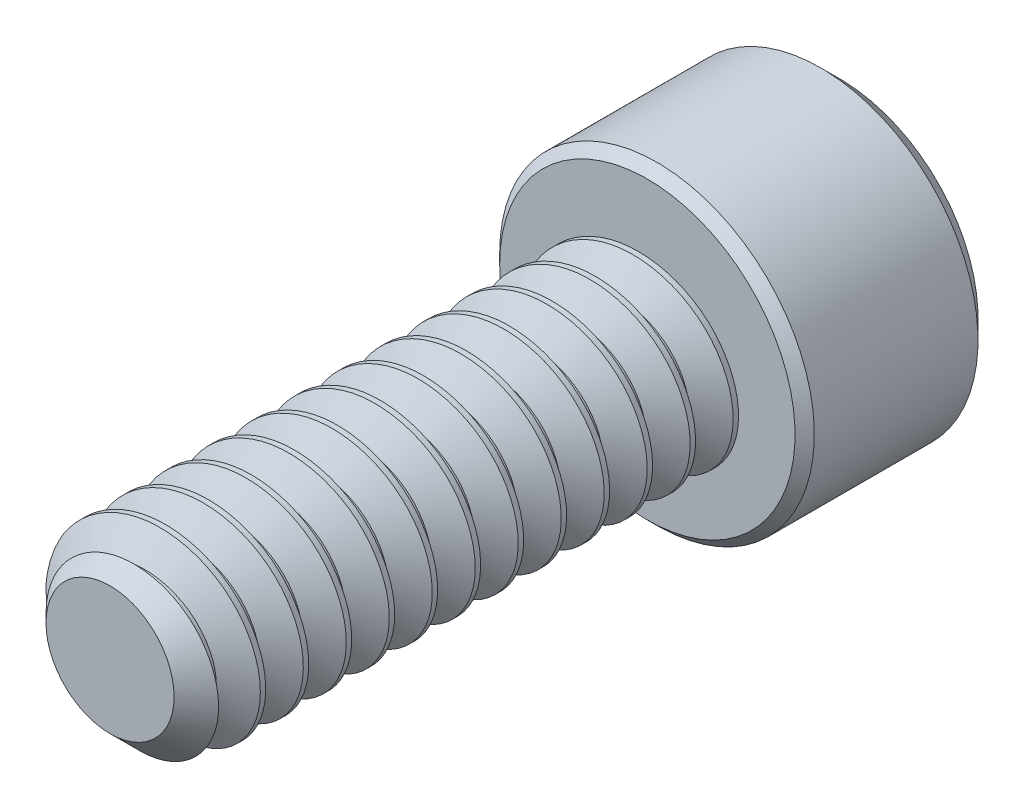
SolidWorks part; units mm, degrees
ref_plane "Front Plane" through (0, 0, 0) normal (0, 0, 1) x (1, 0, 0)
ref_plane "Top Plane" through (0, 0, 0) normal (0, 1, 0) x (1, 0, 0)
ref_plane "Right Plane" through (0, 0, 0) normal (1, 0, 0) x (0, 0, -1)
sketch "Sketch1" plane through (0, 0, 0) normal (0, 0, 1) x (1, 0, 0)
  line L0 (0, 1.4224) -> (0, -1.4224) construction
  circle A0 centre (0, 0) radius 1.4224
  dimension "OD" = 2.8448
extrude "Extrude1" add sketch "Sketch1" against normal blind 7.9375
sketch "Sketch2" plane through (0, 0, 0) normal (0, 0, 1) x (1, 0, 0)
  circle A0 centre (0, 0) radius 1.4224 construction
  circle A1 centre (0, 0) radius 1.4224
curve "Helix/Spiral1" pitch 0.635 height 8.5725 radius 1.4224 centre (0, 0, 0) axis (0, 0, -1) start towards (0, 1, 0) parameters "pitch"=0.635
chamfer "Chamfer3" distance 0.4763 angle 45 1 edges at (1.4224, 0, 0)
sketch "Sketch3" plane through (0, 0, 0) normal (1, 0, 0) x (0, 0, -1)
  line L0 (-0.5556, 1.4224) -> (-0.3175, 1.01)
  line L1 (-0.3175, 1.01) -> (-0.2381, 1.01)
  line L2 (-0.2381, 1.01) -> (0, 1.4224)
  line L3 (-0.5556, 1.4224) -> (0, 1.4224)
  line L4 (-0.2778, 1.4224) -> (-0.2778, 1.01) construction
  line L5 (-0.4366, 1.2162) -> (-0.1191, 1.2162) construction
  line L6 (0, 1.4224) -> (0, -1.4224) construction
  dimension "D1" = 0.0794
  dimension "D2" = 0.3175
  dimension "D3" = 60
sweep "Cut-Sweep1" cut profiles "Sketch3" path "Helix/Spiral1"
sketch "Sketch6" plane through (0, 0, -7.9375) normal (0, 0, -1) x (-1, 0, 0)
  circle A0 centre (0, 0) radius 2.3241
  dimension "head dia" = 4.6482
extrude "Extrude2" add sketch "Sketch6" along normal blind 2.8448
sketch "Sketch7" plane through (0, 0, -10.7823) normal (0, 0, -1) x (-1, 0, 0)
  line L1 (0, 1.3748) -> (-1.1906, 0.6874)
  line L2 (-1.1906, 0.6874) -> (-1.1906, -0.6874)
  line L3 (-1.1906, -0.6874) -> (0, -1.3748)
  line L4 (0, -1.3748) -> (1.1906, -0.6874)
  line L5 (1.1906, -0.6874) -> (1.1906, 0.6874)
  line L6 (1.1906, 0.6874) -> (0, 1.3748)
  circle A0 centre (0, 0) radius 1.1906 construction
  dimension "hex dia" = 2.3813
extrude "Cut-Extrude1" cut sketch "Sketch7" against normal blind 1.7859
sketch "Sketch8" plane through (0, 0, -10.7823) normal (0, 0, -1) x (-1, 0, 0)
  circle A0 centre (0, 0) radius 1.3748
extrude "Cut-Extrude2" cut sketch "Sketch8" against normal blind 0.2845 draft 45
chamfer "Chamfer1" distance 0.2845 angle 45 1 edges at (-2.3241, 0, -10.7823)
chamfer "Chamfer2" distance 0.1422 angle 45 1 edges at (-2.3241, 0, -7.9375)
sketch "Sketch9" plane through (0, 0, 0) normal (1, 0, 0) x (0, 0, -1)
  line L0 (0, 1.4224) -> (0, -1.4224) construction
  line L1 (3.4925, 1.4224) -> (3.4925, -1.4224) construction
  line L2 (7.9375, 2.3241) -> (7.9375, -2.3241) construction
  line L3 (10.7823, 2.3241) -> (10.7823, -2.3241) construction
  line L4 (10.7823, 0) -> (0, 0) construction
  dimension "D1" = 3.4925
  dimension "D2" = 2.8448
  dimension "D3" = 4.6482
  dimension "D4" = 7.9375
equation "\"D3@Helix/Spiral1\" = \"screw length@Extrude1\"+\"pitch@Helix/Spiral1\""
equation "\"D1@Sketch3\" = \"pitch@Helix/Spiral1\"*.125"
equation "\"D2@Sketch3\" = \"pitch@Helix/Spiral1\"*.5"
equation "\"D1@Cut-Extrude1\" = \"hex dia@Sketch7\"*.75"
equation "\"D1@Chamfer1\" = \"head depth@Extrude2\"/10"
equation "\"D1@Sketch9\" = \"pitch@Helix/Spiral1\"*5.5"
equation "\"D1@Chamfer2\" = \"D1@Chamfer1\"/2"
equation "\"D1@Cut-Extrude2\" = \"D1@Chamfer2\"*2"
equation "\"D1@Chamfer3\" = \"pitch@Helix/Spiral1\"*.750"
equation "\"D2@Sketch9\" = \"head depth@Extrude2\""
equation "\"D3@Sketch9\" = \"head dia@Sketch6\""
equation "\"D4@Sketch9\" = \"screw length@Extrude1\""
